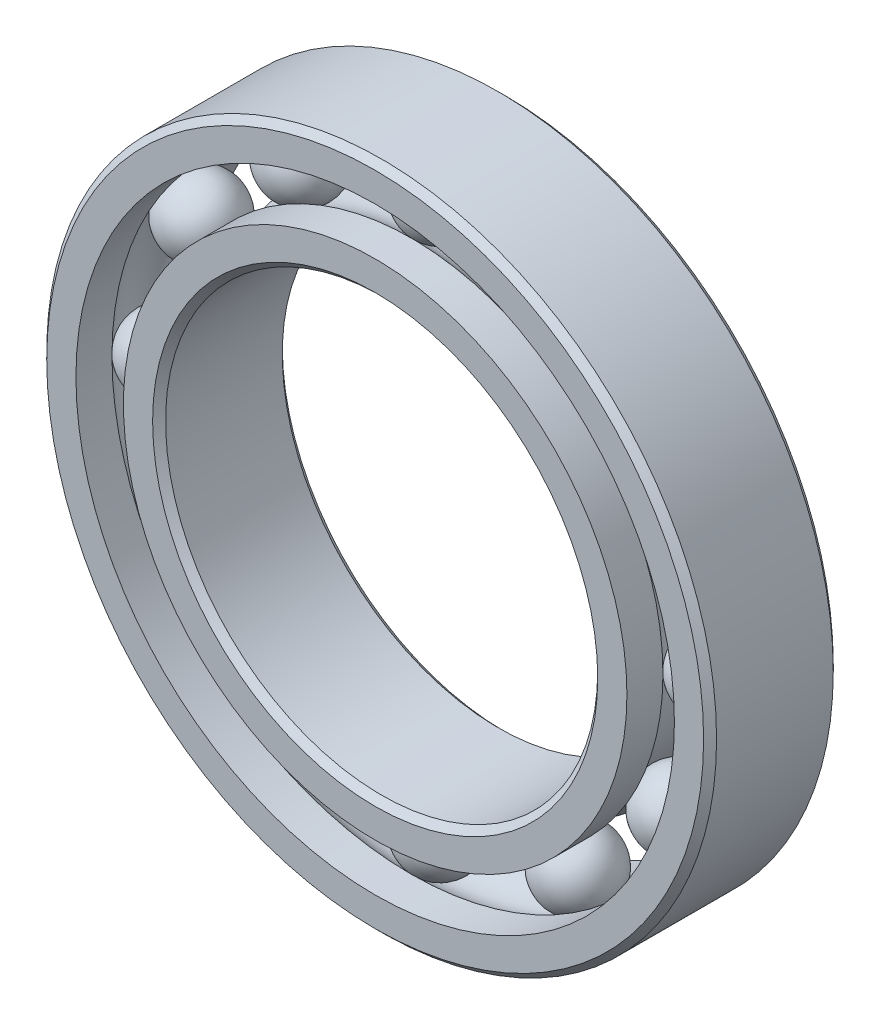
SolidWorks part; units mm, degrees
ref_plane "Front Plane" through (0, 0, 0) normal (0, 0, 1) x (1, 0, 0)
ref_plane "Top Plane" through (0, 0, 0) normal (0, 1, 0) x (1, 0, 0)
ref_plane "Right Plane" through (0, 0, 0) normal (1, 0, 0) x (0, 0, -1)
sketch "Sketch1" plane through (0, 0, 0) normal (1, 0, 0) x (0, 0, -1)
  line L0 (-6, 0) -> (6, 0) construction
  line L1 (0, 31) -> (0, -31) construction
  line L2 (5.4, 31) -> (-5.4, 31)
  line L3 (-5.4, 31) -> (-6, 30.4)
  line L4 (-6, 30.4) -> (-6, 27.6976)
  line L5 (-6, 27.6976) -> (-2.6667, 27.6976)
  line L6 (6, 27.6976) -> (2.6667, 27.6976)
  line L7 (6, 30.4) -> (6, 27.6976)
  line L8 (5.4, 31) -> (6, 30.4)
  line L9 (0, 31) -> (0, 25.4998) construction
  line L10 (0, 25.4998) -> (0, 19.9995) construction
  arc A0 (-2.6667, 27.6976) -> (2.6667, 27.6976) centre (0, 25.4998) cw
  point P14 (0, 19.9995)
  dimension "Width" = 12
  dimension "OD" = 62
  dimension "D1" = 45
  dimension "D2" = 0.6
  dimension "Shaft Dia" = 39.999
  dimension "D3" = 5.3333
  dimension "D4" = 2.1978
revolve "Revolve1" add sketch "Sketch1" angle 360 about L0
sketch "Sketch3" plane through (0, 0, 0) normal (1, 0, 0) x (0, 0, -1)
  line L0 (-6, 23.3019) -> (-2.6667, 23.3019)
  line L1 (0, 31) -> (0, -31) construction
  line L2 (-6, 30.4) -> (-6, 27.6976) construction
  line L3 (-6, 23.3019) -> (-6, 20.5995)
  line L4 (-5.4, 31) -> (-6, 30.4) construction
  line L5 (-6, 20.5995) -> (-5.4, 19.9995)
  line L6 (-5.4, 19.9995) -> (5.4, 19.9995)
  line L7 (5.4, 31) -> (5.4, -31) construction
  line L8 (5.4, 19.9995) -> (6, 20.5995)
  line L9 (6, -30.4) -> (6, 30.4) construction
  line L10 (6, 20.5995) -> (6, 23.3019)
  line L11 (6, 23.3019) -> (2.6667, 23.3019)
  line L13 (5.4, 31) -> (6, 30.4) construction
  arc A0 (2.6667, 27.6976) -> (-2.6667, 27.6976) centre (0, 25.4998) ccw construction
  arc A1 (2.6667, 23.3019) -> (-2.6667, 23.3019) centre (0, 25.4997) cw
revolve "Revolve3" add sketch "Sketch3" angle 360 about L0
sketch "Sketch4" plane through (0, 0, 0) normal (1, 0, 0) x (0, 0, -1)
  line L0 (-3.4556, 25.4998) -> (3.4556, 25.4998)
  arc A2 (-3.4556, 25.4998) -> (3.4556, 25.4998) centre (0, 25.4998) cw
  arc A3 (2.6667, 27.6976) -> (-2.6667, 27.6976) centre (0, 25.4998) ccw construction
revolve "Revolve4" add sketch "Sketch4" angle 360 about L0
ref_axis "Axis1" through (0, 0, -6) along (0, 0, 1)
pattern_circular "CirPattern1" count 12 every 30 about axis through (0, 0, -6) along (0, 0, 1) of bodies 104
sketch "Sketch5" plane through (0, 0, 0) normal (1, 0, 0) x (0, 0, -1)
  line L0 (-6, 27.6976) -> (-2.6667, 27.6976) construction
  line L1 (-5.7, 27.6976) -> (-3.4556, 27.6976)
  line L2 (-5.7, 27.6976) -> (-5.7, 23.3019)
  line L3 (-5.7, 23.3019) -> (-3.4556, 23.3019)
  line L4 (-3.4556, 27.6976) -> (-3.4556, 23.3019)
  line L5 (-6, 23.3019) -> (-2.6667, 23.3019) construction
  line L6 (6, 27.6976) -> (2.6667, 27.6976) construction
  line L7 (5.7, 27.6976) -> (3.4556, 27.6976)
  line L8 (5.7, 27.6976) -> (5.7, 23.3019)
  line L9 (5.7, 23.3019) -> (3.4556, 23.3019)
  line L10 (3.4556, 27.6976) -> (3.4556, 23.3019)
  line L11 (6, 23.3019) -> (2.6667, 23.3019) construction
  line L12 (-5.4, 31) -> (-6, 30.4) construction
  point P18 (-5.7, 30.7)
equation "\"D2@Sketch1\" = \"Width@Sketch1\"*.05"
equation "\"D3@Sketch1\" = \"Width@Sketch1\"/2.25"
equation "\"D4@Sketch1\" = (((\"OD@Sketch1\"-\"Width@Sketch1\")/2)/3.25)/3.5"
equation "\"D2@CirPattern1\" = 360/\"Balls@CirPattern1\""
